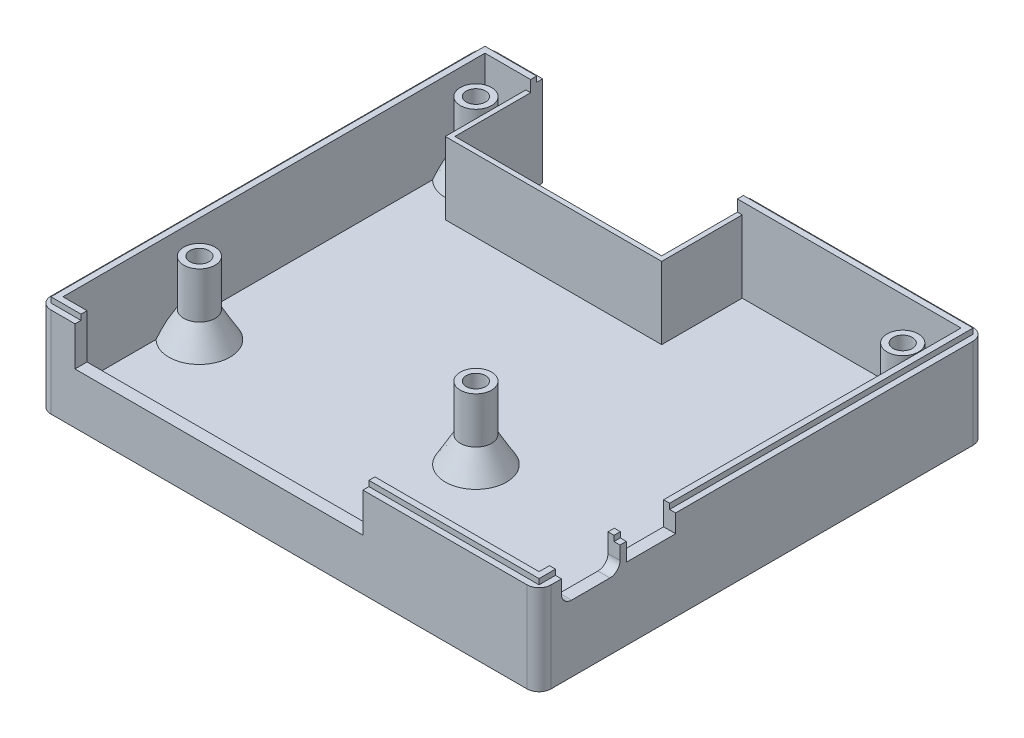
SolidWorks part; units mm, degrees
ref_plane "Front Plane" through (0, 0, 0) normal (0, 0, 1) x (1, 0, 0)
ref_plane "Top Plane" through (0, 0, 0) normal (0, 1, 0) x (1, 0, 0)
ref_plane "Right Plane" through (0, 0, 0) normal (1, 0, 0) x (0, 0, -1)
sketch "Sketch1" plane through (0, 0, 0) normal (0, 1, 0) x (1, 0, 0)
  line L1 (0, 0) -> (83.2, 0)
  line L2 (0, 0) -> (0, 74.2)
  line L3 (0, 74.2) -> (83.2, 74.2)
  line L4 (83.2, 0) -> (83.2, 74.2)
  dimension "D1" = 74.2
  dimension "D2" = 83.2
extrude "Boss-Extrude1" add sketch "Sketch1" along normal blind 15
shell "Shell1" thickness 2 removed face at (41.6, 15, -37.1)
sketch "Sketch2" plane through (0, 0, -2) normal (0, 0, -1) x (-1, 0, 0)
  line L0 (-2, 15) -> (-2, 2) construction
  line L1 (-6, 8.5) -> (-53.9, 8.5)
  line L2 (-6, 8.5) -> (-6, 15)
  line L3 (-6, 15) -> (-53.9, 15)
  line L4 (-53.9, 8.5) -> (-53.9, 15)
  line L6 (-2, 15) -> (-81.2, 15) construction
  dimension "D1" = 4
  dimension "D2" = 47.9
  dimension "D3" = 6.5
extrude "Cut-Extrude1" cut sketch "Sketch2" against normal through all
sketch "Sketch3" plane through (81.2, 0, 0) normal (-1, 0, 0) x (0, 0, 1)
  line L0 (-13.07, 12.775) -> (-13.07, 13.375) construction
  line L1 (-13.07, 12.775) -> (-13.07, 13.375) construction
  line L2 (-5.41, 11.495) -> (-11.79, 11.495) construction
  line L3 (-5.41, 11.495) -> (-11.79, 11.495) construction
  line L12 (-4.13, 13.375) -> (-4.13, 12.775) construction
  line L13 (-4.13, 13.375) -> (-4.13, 12.775) construction
  line L14 (-5.41, 14.655) -> (-11.79, 14.655) construction
  line L15 (-13.47, 12.775) -> (-13.47, 13.375)
  line L17 (-3.73, 13.375) -> (-3.73, 12.775)
  line L18 (-5.41, 11.095) -> (-11.79, 11.095)
  line L19 (-13.47, 13.375) -> (-13.47, 15)
  line L20 (-2, 15) -> (-72.2, 15) construction
  line L21 (-13.47, 15) -> (-3.73, 15)
  line L22 (-3.73, 15) -> (-3.73, 13.375)
  line L24 (-5.41, 15.055) -> (-11.79, 15.055) construction
  arc A0 (-13.07, 12.775) -> (-11.79, 11.495) centre (-11.79, 12.775) ccw construction
  arc A1 (-11.79, 14.655) -> (-13.07, 13.375) centre (-11.79, 13.375) ccw construction
  arc A2 (-13.07, 12.775) -> (-11.79, 11.495) centre (-11.79, 12.775) ccw construction
  arc A3 (-11.79, 14.655) -> (-13.07, 13.375) centre (-11.79, 13.375) ccw construction
  arc A4 (-5.41, 11.495) -> (-4.13, 12.775) centre (-5.41, 12.775) ccw construction
  arc A5 (-5.41, 11.495) -> (-4.13, 12.775) centre (-5.41, 12.775) ccw construction
  arc A6 (-4.13, 13.375) -> (-5.41, 14.655) centre (-5.41, 13.375) ccw construction
  arc A7 (-4.13, 13.375) -> (-5.41, 14.655) centre (-5.41, 13.375) ccw construction
  arc A10 (-5.41, 11.095) -> (-3.73, 12.775) centre (-5.41, 12.775) ccw
  arc A11 (-13.47, 12.775) -> (-11.79, 11.095) centre (-11.79, 12.775) ccw
  arc A12 (-11.79, 15.055) -> (-13.47, 13.375) centre (-11.79, 13.375) ccw construction
  arc A13 (-3.73, 13.375) -> (-5.41, 15.055) centre (-5.41, 13.375) ccw construction
  dimension "D1" = 0.4
extrude "Cut-Extrude3" cut sketch "Sketch3" against normal through all contours L15 L19 L21 L22 L17 A10 L18 A11
sketch "Sketch4" plane through (81.2, 0, 0) normal (-1, 0, 0) x (0, 0, 1)
  line L0 (-13.47, 15) -> (-72.2, 15) construction
  line L1 (-14.52, 15) -> (-22.72, 15)
  line L2 (-14.52, 15) -> (-14.52, 12)
  line L3 (-14.52, 12) -> (-22.72, 12)
  line L4 (-22.72, 15) -> (-22.72, 12)
  line L5 (-13.47, 12.775) -> (-13.47, 15) construction
  dimension "D1" = 8.2
  dimension "D2" = 3
  dimension "D3" = 1.05
extrude "Cut-Extrude4" cut sketch "Sketch4" against normal through all
sketch "Sketch5" plane through (0, 2, 0) normal (0, 1, 0) x (1, 0, 0)
  line L0 (2, 2) -> (81.2, 2) construction
  line L1 (81.2, 2) -> (81.2, 72.2) construction
  circle A0 centre (77.9, 27) radius 1.5
  dimension "D1" = 25
  dimension "D2" = 3.3
  dimension "D3" = 3
extrude "Cut-Extrude5" cut sketch "Sketch5" against normal through all
sketch "Sketch6" plane through (0, 0, 0) normal (0, -1, 0) x (1, 0, 0)
  line L0 (83.2, -74.2) -> (0, -74.2) construction
  line L1 (9.6, -74.2) -> (44, -74.2)
  line L2 (9.6, -74.2) -> (9.6, -59.6)
  line L3 (9.6, -59.6) -> (44, -59.6)
  line L4 (44, -74.2) -> (44, -59.6)
  line L5 (0, -74.2) -> (0, 0) construction
  dimension "D1" = 9.6
  dimension "D2" = 44
  dimension "D3" = 14.6
extrude "Cut-Extrude6" cut sketch "Sketch6" against normal through all
sketch "Sketch7" plane through (0, 2, 0) normal (0, 1, 0) x (1, 0, 0)
  line L0 (44, 72.2) -> (44, 59.6) construction
  line L1 (44, 59.6) -> (9.6, 59.6) construction
  line L2 (9.6, 59.6) -> (9.6, 72.2) construction
  line L3 (44, 72.2) -> (44, 59.6)
  line L4 (44, 59.6) -> (9.6, 59.6)
  line L5 (9.6, 59.6) -> (9.6, 72.2)
  line L6 (44.8, 72.2) -> (44.8, 58.8)
  line L7 (44.8, 58.8) -> (8.8, 58.8)
  line L8 (8.8, 58.8) -> (8.8, 72.2)
  line L9 (8.8, 72.2) -> (9.6, 72.2)
  line L10 (44, 72.2) -> (44.8, 72.2)
  dimension "D1" = 0.8
extrude "Boss-Extrude2" add sketch "Sketch7" along normal blind 12
sketch "Sketch9" plane through (0, 15, 0) normal (0, 1, 0) x (1, 0, 0)
  line L0 (9.6, 72.2) -> (2, 72.2) construction
  line L1 (2, 2) -> (6, 2) construction
  line L2 (2, 72.2) -> (2, 2) construction
  line L3 (9.6, 72.2) -> (2, 72.2)
  line L4 (2, 2) -> (6, 2)
  line L5 (2, 72.2) -> (2, 2)
  line L6 (53.9, 2) -> (81.2, 2) construction
  line L7 (81.2, 2) -> (81.2, 3.73) construction
  line L8 (81.2, 13.47) -> (81.2, 14.52) construction
  line L9 (81.2, 22.72) -> (81.2, 72.2) construction
  line L10 (81.2, 72.2) -> (44, 72.2) construction
  line L11 (53.9, 2) -> (81.2, 2)
  line L12 (81.2, 2) -> (81.2, 3.73)
  line L13 (81.2, 13.47) -> (81.2, 14.52)
  line L14 (81.2, 22.72) -> (81.2, 72.2)
  line L15 (81.2, 72.2) -> (44, 72.2)
extrude "Extrude-Thin1" add sketch "Sketch9" along normal blind 0.9 thin thin type one direction wall 1
fillet "Fillet1" radius 2 4 edges at (0, 7.5, 0) (83.2, 7.5, 0) (83.2, 7.5, -74.2) (0, 7.5, -74.2)
sketch "Sketch10" plane through (0, 2, 0) normal (0, 1, 0) x (1, 0, 0)
  line L0 (2, 64.4) -> (2, 69.8) construction
  line L1 (2, 18.4) -> (2, 23.8) construction
  line L2 (2, 64.4) -> (2, 69.8) construction
  line L3 (2, 18.4) -> (2, 23.8) construction
  circle A0 centre (76.6, 67.1) radius 4.5 construction
  circle A1 centre (46.6, 26.1) radius 4.5
  circle A2 centre (46.6, 26.1) radius 4.5 construction
  arc A3 (2, 64.4) -> (2, 69.8) centre (5.6, 67.1) ccw construction
  arc A4 (2, 18.4) -> (2, 23.8) centre (5.6, 21.1) ccw construction
  circle A5 centre (76.6, 67.1) radius 4.5 construction
  arc A6 (2, 64.4) -> (2, 69.8) centre (5.6, 67.1) ccw construction
  arc A7 (2, 18.4) -> (2, 23.8) centre (5.6, 21.1) ccw construction
  circle A8 centre (5.6, 67.1) radius 1.6
  circle A9 centre (76.6, 67.1) radius 1.6
  circle A10 centre (46.6, 26.1) radius 1.6
  circle A11 centre (5.6, 21.1) radius 1.6
  circle A12 centre (5.6, 21.1) radius 2.6
  circle A13 centre (46.6, 26.1) radius 2.6
  circle A14 centre (76.6, 67.1) radius 2.6
  circle A15 centre (5.6, 67.1) radius 2.6
  dimension "D2" = 3.2
  dimension "D3" = 1
  dimension "D1" = 0
extrude "Boss-Extrude3" add sketch "Sketch10" along normal blind 12 contours A15 | A8 | A14 | A9 | A13 | A10 | A12 | A11
chamfer "Chamfer1" distance 2.5 angle 60 4 edges at (5.6, 2, -69.7) (76.6, 2, -69.7) (46.6, 2, -28.7) (5.6, 2, -23.7) first distance on face at (5.6, 2, -23.7)
sketch "Sketch11" plane through (0, 0, 0) normal (0, -1, 0) x (1, 0, 0)
  circle A0 centre (76.6, -67.1) radius 2.6 construction
  circle A1 centre (5.6, -67.1) radius 2.6 construction
  circle A2 centre (5.6, -21.1) radius 2.6 construction
  circle A3 centre (46.6, -26.1) radius 2.6 construction
  circle A4 centre (76.6, -67.1) radius 2.6 construction
  circle A5 centre (5.6, -67.1) radius 2.6 construction
  circle A6 centre (5.6, -21.1) radius 2.6 construction
  circle A7 centre (46.6, -26.1) radius 2.6 construction
  circle A8 centre (5.6, -67.1) radius 2.85
  circle A9 centre (5.6, -21.1) radius 2.85
  circle A10 centre (46.6, -26.1) radius 2.85
  circle A11 centre (76.6, -67.1) radius 2.85
  dimension "D1" = 5.7
extrude "Cut-Extrude7" cut sketch "Sketch11" against normal blind 3.1
